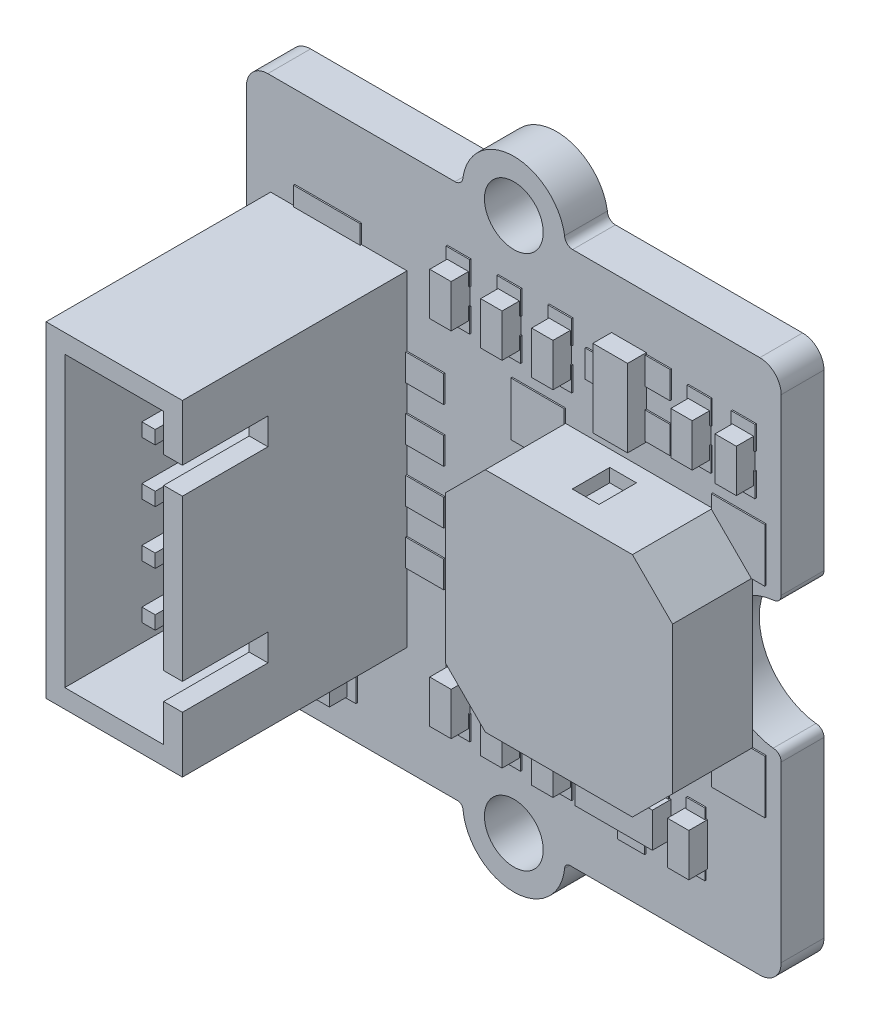
SolidWorks part; units mm, degrees
other "Buzzer_MLT8530"
other "Connecteur_Grove"
other "PCB_Seeed_107020109"
ref_plane "Plan de face" through (0, 0, 0) normal (0, 0, 1) x (1, 0, 0)
ref_plane "Plan de dessus" through (0, 0, 0) normal (0, 1, 0) x (1, 0, 0)
ref_plane "Plan de droite" through (0, 0, 0) normal (1, 0, 0) x (0, 0, -1)
sketch "Esquisse1" plane through (0, 0, 0) normal (0, 0, 1) x (1, 0, 0)
  line L0 (-9.1873, -9.9873) -> (-2.0873, -9.9873)
  line L1 (-9.1873, 10.0127) -> (-2.1873, 10.0127)
  line L2 (-9.9873, -2.6873) -> (-9.9873, -9.1873)
  line L3 (-9.9873, 2.7127) -> (-9.9873, 9.2127)
  line L4 (9.2127, -9.9873) -> (2.1127, -9.9873)
  line L5 (10.0127, 2.7127) -> (10.0127, 9.2127)
  line L6 (10.0127, -2.6873) -> (10.0127, -9.1873)
  line L7 (2.2127, 10.0127) -> (9.2127, 10.0127)
  arc A0 (-9.1873, 10.0127) -> (-9.9873, 9.2127) centre (-9.1873, 9.2127) ccw
  arc A1 (-9.9873, -9.1873) -> (-9.1873, -9.9873) centre (-9.1873, -9.1873) ccw
  arc A2 (9.2127, -9.9873) -> (10.0127, -9.1873) centre (9.2127, -9.1873) ccw
  arc A3 (9.2127, 10.0127) -> (10.0127, 9.2127) centre (9.2127, 9.2127) cw
  arc A4 (-2.0873, -9.9873) -> (-1.8873, -10.1873) centre (-2.0873, -10.1873) cw
  arc A5 (2.1127, -9.9873) -> (1.9127, -10.1873) centre (2.1127, -10.1873) ccw
  arc A6 (1.9127, -10.1873) -> (-1.8873, -10.1873) centre (0.0127, -9.9873) cw
  arc A7 (-2.1873, 10.0127) -> (-1.8873, 10.3127) centre (-2.1873, 10.3127) ccw
  arc A8 (2.2127, 10.0127) -> (1.9127, 10.3127) centre (2.2127, 10.3127) cw
  arc A9 (-1.8873, 10.3127) -> (1.9127, 10.3127) centre (0.0127, 10.0127) cw
  arc A10 (-9.9873, 2.7127) -> (-9.6873, 2.4127) centre (-9.6873, 2.7127) ccw
  arc A11 (-9.9873, -2.6873) -> (-9.6873, -2.3873) centre (-9.6873, -2.6873) cw
  arc A12 (-9.6873, -2.3873) -> (-9.6873, 2.4127) centre (-9.9873, 0.0127) ccw
  arc A13 (10.0127, -2.6873) -> (9.7127, -2.3873) centre (9.7127, -2.6873) ccw
  arc A14 (10.0127, 2.7127) -> (9.7127, 2.4127) centre (9.7127, 2.7127) cw
  arc A15 (9.7127, 2.4127) -> (9.7127, -2.3873) centre (10.0127, 0.0127) ccw
  circle A16 centre (0.0127, -9.9873) radius 1.1
  circle A17 centre (0.0127, 10.0127) radius 1.1
extrude "PCB_contour_Eagle_ep_ESTIMEE_1_6" add sketch "Esquisse1" along normal blind 1.6 separate body
sketch "Esquisse2" plane through (0, 0, 0) normal (0, 0, 1) x (1, 0, 0)
  line L1 (-9.083, -5.973) -> (-3.983, -5.973)
  line L2 (-9.083, -5.973) -> (-9.083, 6.227)
  line L3 (-9.083, 6.227) -> (-3.983, 6.227)
  line L4 (-3.983, -5.973) -> (-3.983, 6.227)
extrude "Grove_position_Eagle_H_ESTIMEE" add sketch "Esquisse2" along normal blind 8.4 from offset 1.6 separate body
sketch "Esquisse3" plane through (0, 0, 0) normal (0, 0, 1) x (1, 0, 0)
  line L1 (-8.383, -5.273) -> (-4.683, -5.273)
  line L2 (-8.383, -5.273) -> (-8.383, 5.527)
  line L3 (-8.383, 5.527) -> (-4.683, 5.527)
  line L4 (-4.683, -5.273) -> (-4.683, 5.527)
extrude "Cavite_connecteur" cut sketch "Esquisse3" against normal blind 7.3 from offset 10
sketch "Esquisse4" plane through (0, 0, 0) normal (0, 0, 1) x (1, 0, 0)
  line L1 (-4.783, -3.873) -> (-3.783, -3.873)
  line L2 (-4.783, -3.873) -> (-4.783, -2.873)
  line L3 (-4.783, -2.873) -> (-3.783, -2.873)
  line L4 (-3.783, -3.873) -> (-3.783, -2.873)
  line L6 (-4.783, 3.127) -> (-3.783, 3.127)
  line L7 (-4.783, 3.127) -> (-4.783, 4.127)
  line L8 (-4.783, 4.127) -> (-3.783, 4.127)
  line L9 (-3.783, 3.127) -> (-3.783, 4.127)
extrude "Detrompeurs_ESTIMES" cut sketch "Esquisse4" against normal blind 3.2 from offset 10
sketch "Esquisse5" plane through (0, 0, 0) normal (0, 0, 1) x (1, 0, 0)
  line L1 (-6.9, -3.123) -> (-6.4, -3.123)
  line L2 (-6.9, -3.123) -> (-6.9, -2.623)
  line L3 (-6.9, -2.623) -> (-6.4, -2.623)
  line L4 (-6.4, -3.123) -> (-6.4, -2.623)
  line L6 (-6.9, -1.123) -> (-6.4, -1.123)
  line L7 (-6.9, -1.123) -> (-6.9, -0.623)
  line L8 (-6.9, -0.623) -> (-6.4, -0.623)
  line L9 (-6.4, -1.123) -> (-6.4, -0.623)
  line L11 (-6.9, 0.877) -> (-6.4, 0.877)
  line L12 (-6.9, 0.877) -> (-6.9, 1.377)
  line L13 (-6.9, 1.377) -> (-6.4, 1.377)
  line L14 (-6.4, 0.877) -> (-6.4, 1.377)
  line L16 (-6.9, 2.877) -> (-6.4, 2.877)
  line L17 (-6.9, 2.877) -> (-6.9, 3.377)
  line L18 (-6.9, 3.377) -> (-6.4, 3.377)
  line L19 (-6.4, 2.877) -> (-6.4, 3.377)
extrude "Contacts_Grove_pas_2mm" add sketch "Esquisse5" along normal blind 5.9 from offset 2.7 separate body
sketch "Esquisse6" plane through (0, 0, 0) normal (0, 0, 1) x (1, 0, 0)
  line L0 (1.949, -4.25) -> (7.449, -4.25)
  line L1 (7.449, -4.25) -> (8.949, -2.75)
  line L2 (8.949, -2.75) -> (8.949, 2.75)
  line L3 (8.949, 2.75) -> (7.449, 4.25)
  line L4 (7.449, 4.25) -> (1.949, 4.25)
  line L5 (1.949, 4.25) -> (0.449, 2.75)
  line L6 (0.449, 2.75) -> (0.449, -2.75)
  line L7 (0.449, -2.75) -> (1.949, -4.25)
extrude "MLT8530_8_5x8_5x3" add sketch "Esquisse6" along normal blind 3 from offset 1.6 separate body
sketch "Esquisse7" plane through (0, 0, 0) normal (0, 0, 1) x (1, 0, 0)
  line L1 (4.199, 3.75) -> (5.199, 3.75)
  line L2 (4.199, 3.75) -> (4.199, 4.55)
  line L3 (4.199, 4.55) -> (5.199, 4.55)
  line L4 (5.199, 3.75) -> (5.199, 4.55)
extrude "Sortie_son_laterale_ESTIMEE" cut sketch "Esquisse7" against normal blind 1.4 from offset 3.6
sketch "Esquisse8" plane through (0, 0, 0) normal (0, 0, 1) x (1, 0, 0)
  line L1 (-0.527, 5.804) -> (0.273, 5.804)
  line L2 (-0.527, 5.804) -> (-0.527, 7.404)
  line L3 (-0.527, 7.404) -> (0.273, 7.404)
  line L4 (0.273, 5.804) -> (0.273, 7.404)
extrude "C1_position_Eagle_H_simplifiee" add sketch "Esquisse8" along normal blind 0.7 from offset 1.6 separate body
sketch "Esquisse9" plane through (0, 0, 0) normal (0, 0, 1) x (1, 0, 0)
  line L1 (-2.432, 5.804) -> (-1.632, 5.804)
  line L2 (-2.432, 5.804) -> (-2.432, 7.404)
  line L3 (-2.432, 7.404) -> (-1.632, 7.404)
  line L4 (-1.632, 5.804) -> (-1.632, 7.404)
extrude "C2_position_Eagle_H_simplifiee" add sketch "Esquisse9" along normal blind 0.7 from offset 1.6 separate body
sketch "Esquisse10" plane through (0, 0, 0) normal (0, 0, 1) x (1, 0, 0)
  line L1 (2.995, -7.254) -> (5.895, -7.254)
  line L2 (2.995, -7.254) -> (2.995, -5.954)
  line L3 (2.995, -5.954) -> (5.895, -5.954)
  line L4 (5.895, -7.254) -> (5.895, -5.954)
extrude "Q1_position_Eagle_H_simplifiee" add sketch "Esquisse10" along normal blind 0.7 from offset 1.6 separate body
sketch "Esquisse11" plane through (0, 0, 0) normal (0, 0, 1) x (1, 0, 0)
  line L1 (-0.527, -7.404) -> (0.273, -7.404)
  line L2 (-0.527, -7.404) -> (-0.527, -5.804)
  line L3 (-0.527, -5.804) -> (0.273, -5.804)
  line L4 (0.273, -7.404) -> (0.273, -5.804)
extrude "R1_position_Eagle_H_simplifiee" add sketch "Esquisse11" along normal blind 0.7 from offset 1.6 separate body
sketch "Esquisse12" plane through (0, 0, 0) normal (0, 0, 1) x (1, 0, 0)
  line L1 (3.668, 5.154) -> (4.968, 5.154)
  line L2 (3.668, 5.154) -> (3.668, 8.054)
  line L3 (3.668, 8.054) -> (4.968, 8.054)
  line L4 (4.968, 5.154) -> (4.968, 8.054)
extrude "U1_position_Eagle_H_simplifiee" add sketch "Esquisse12" along normal blind 0.7 from offset 1.6 separate body
sketch "Esquisse13" plane through (0, 0, 0) normal (0, 0, 1) x (1, 0, 0)
  line L1 (1.378, 5.804) -> (2.178, 5.804)
  line L2 (1.378, 5.804) -> (1.378, 7.404)
  line L3 (1.378, 7.404) -> (2.178, 7.404)
  line L4 (2.178, 5.804) -> (2.178, 7.404)
extrude "C3_position_Eagle_H_simplifiee" add sketch "Esquisse13" along normal blind 0.7 from offset 1.6 separate body
sketch "Esquisse14" plane through (0, 0, 0) normal (0, 0, 1) x (1, 0, 0)
  line L1 (8.236, 5.804) -> (9.036, 5.804)
  line L2 (8.236, 5.804) -> (8.236, 7.404)
  line L3 (8.236, 7.404) -> (9.036, 7.404)
  line L4 (9.036, 5.804) -> (9.036, 7.404)
extrude "C5_position_Eagle_H_simplifiee" add sketch "Esquisse14" along normal blind 0.7 from offset 1.6 separate body
sketch "Esquisse15" plane through (0, 0, 0) normal (0, 0, 1) x (1, 0, 0)
  line L1 (6.585, 5.804) -> (7.385, 5.804)
  line L2 (6.585, 5.804) -> (6.585, 7.404)
  line L3 (6.585, 7.404) -> (7.385, 7.404)
  line L4 (7.385, 5.804) -> (7.385, 7.404)
extrude "C4_position_Eagle_H_simplifiee" add sketch "Esquisse15" along normal blind 0.7 from offset 1.6 separate body
sketch "Esquisse16" plane through (0, 0, 0) normal (0, 0, 1) x (1, 0, 0)
  line L1 (-2.432, -7.404) -> (-1.632, -7.404)
  line L2 (-2.432, -7.404) -> (-2.432, -5.804)
  line L3 (-2.432, -5.804) -> (-1.632, -5.804)
  line L4 (-1.632, -7.404) -> (-1.632, -5.804)
extrude "R2_position_Eagle_H_simplifiee" add sketch "Esquisse16" along normal blind 0.7 from offset 1.6 separate body
sketch "Esquisse17" plane through (0, 0, 0) normal (0, 0, 1) x (1, 0, 0)
  line L1 (-7.785, -8.655) -> (-6.185, -8.655)
  line L2 (-7.785, -8.655) -> (-7.785, -7.855)
  line L3 (-7.785, -7.855) -> (-6.185, -7.855)
  line L4 (-6.185, -8.655) -> (-6.185, -7.855)
extrude "D1_position_Eagle_H_simplifiee" add sketch "Esquisse17" along normal blind 0.7 from offset 1.6 separate body
sketch "Esquisse18" plane through (0, 0, 0) normal (0, 0, 1) x (1, 0, 0)
  line L1 (6.458, -7.531) -> (7.258, -7.531)
  line L2 (6.458, -7.531) -> (6.458, -5.931)
  line L3 (6.458, -5.931) -> (7.258, -5.931)
  line L4 (7.258, -7.531) -> (7.258, -5.931)
extrude "D2_position_Eagle_H_simplifiee" add sketch "Esquisse18" along normal blind 0.7 from offset 1.6 separate body
sketch "Esquisse19" plane through (0, 0, 0) normal (0, 0, 1) x (1, 0, 0)
  line L1 (1.378, -7.404) -> (2.178, -7.404)
  line L2 (1.378, -7.404) -> (1.378, -5.804)
  line L3 (1.378, -5.804) -> (2.178, -5.804)
  line L4 (2.178, -7.404) -> (2.178, -5.804)
extrude "R3_position_Eagle_H_simplifiee" add sketch "Esquisse19" along normal blind 0.7 from offset 1.6 separate body
sketch "Esquisse20" plane through (0, 0, 0) normal (0, 0, 1) x (1, 0, 0)
  line L1 (-0.5715, 6.9215) -> (0.3175, 6.9215)
  line L2 (-0.5715, 6.9215) -> (-0.5715, 7.8105)
  line L3 (-0.5715, 7.8105) -> (0.3175, 7.8105)
  line L4 (0.3175, 6.9215) -> (0.3175, 7.8105)
extrude "Pad_C1_0" add sketch "Esquisse20" along normal blind 0.05 from offset 1.6 separate body
sketch "Esquisse21" plane through (0, 0, 0) normal (0, 0, 1) x (1, 0, 0)
  line L1 (-0.5715, 5.3975) -> (0.3175, 5.3975)
  line L2 (-0.5715, 5.3975) -> (-0.5715, 6.2865)
  line L3 (-0.5715, 6.2865) -> (0.3175, 6.2865)
  line L4 (0.3175, 5.3975) -> (0.3175, 6.2865)
extrude "Pad_C1_1" add sketch "Esquisse21" along normal blind 0.05 from offset 1.6 separate body
sketch "Esquisse22" plane through (0, 0, 0) normal (0, 0, 1) x (1, 0, 0)
  line L1 (-2.4765, 6.9215) -> (-1.5875, 6.9215)
  line L2 (-2.4765, 6.9215) -> (-2.4765, 7.8105)
  line L3 (-2.4765, 7.8105) -> (-1.5875, 7.8105)
  line L4 (-1.5875, 6.9215) -> (-1.5875, 7.8105)
extrude "Pad_C2_0" add sketch "Esquisse22" along normal blind 0.05 from offset 1.6 separate body
sketch "Esquisse23" plane through (0, 0, 0) normal (0, 0, 1) x (1, 0, 0)
  line L1 (-2.4765, 5.3975) -> (-1.5875, 5.3975)
  line L2 (-2.4765, 5.3975) -> (-2.4765, 6.2865)
  line L3 (-2.4765, 6.2865) -> (-1.5875, 6.2865)
  line L4 (-1.5875, 5.3975) -> (-1.5875, 6.2865)
extrude "Pad_C2_1" add sketch "Esquisse23" along normal blind 0.05 from offset 1.6 separate body
sketch "Esquisse24" plane through (0, 0, 0) normal (0, 0, 1) x (1, 0, 0)
  line L1 (-5.06, -3.373) -> (-2.56, -3.373)
  line L2 (-5.06, -3.373) -> (-5.06, -2.373)
  line L3 (-5.06, -2.373) -> (-2.56, -2.373)
  line L4 (-2.56, -3.373) -> (-2.56, -2.373)
extrude "Pad_J1_0" add sketch "Esquisse24" along normal blind 0.05 from offset 1.6 separate body
sketch "Esquisse25" plane through (0, 0, 0) normal (0, 0, 1) x (1, 0, 0)
  line L1 (-5.06, -1.373) -> (-2.56, -1.373)
  line L2 (-5.06, -1.373) -> (-5.06, -0.373)
  line L3 (-5.06, -0.373) -> (-2.56, -0.373)
  line L4 (-2.56, -1.373) -> (-2.56, -0.373)
extrude "Pad_J1_1" add sketch "Esquisse25" along normal blind 0.05 from offset 1.6 separate body
sketch "Esquisse26" plane through (0, 0, 0) normal (0, 0, 1) x (1, 0, 0)
  line L1 (-5.06, 0.627) -> (-2.56, 0.627)
  line L2 (-5.06, 0.627) -> (-5.06, 1.627)
  line L3 (-5.06, 1.627) -> (-2.56, 1.627)
  line L4 (-2.56, 0.627) -> (-2.56, 1.627)
extrude "Pad_J1_2" add sketch "Esquisse26" along normal blind 0.05 from offset 1.6 separate body
sketch "Esquisse27" plane through (0, 0, 0) normal (0, 0, 1) x (1, 0, 0)
  line L1 (-5.06, 2.627) -> (-2.56, 2.627)
  line L2 (-5.06, 2.627) -> (-5.06, 3.627)
  line L3 (-5.06, 3.627) -> (-2.56, 3.627)
  line L4 (-2.56, 2.627) -> (-2.56, 3.627)
extrude "Pad_J1_3" add sketch "Esquisse27" along normal blind 0.05 from offset 1.6 separate body
sketch "Esquisse28" plane through (0, 0, 0) normal (0, 0, 1) x (1, 0, 0)
  line L1 (-8.183, -6.673) -> (-5.683, -6.673)
  line L2 (-8.183, -6.673) -> (-8.183, -4.673)
  line L3 (-8.183, -4.673) -> (-5.683, -4.673)
  line L4 (-5.683, -6.673) -> (-5.683, -4.673)
extrude "Pad_J1_4" add sketch "Esquisse28" along normal blind 0.05 from offset 1.6 separate body
sketch "Esquisse29" plane through (0, 0, 0) normal (0, 0, 1) x (1, 0, 0)
  line L1 (-8.183, 4.927) -> (-5.683, 4.927)
  line L2 (-8.183, 4.927) -> (-8.183, 6.927)
  line L3 (-8.183, 6.927) -> (-5.683, 6.927)
  line L4 (-5.683, 4.927) -> (-5.683, 6.927)
extrude "Pad_J1_5" add sketch "Esquisse29" along normal blind 0.05 from offset 1.6 separate body
sketch "Esquisse30" plane through (0, 0, 0) normal (0, 0, 1) x (1, 0, 0)
  line L1 (3.937, -8.1915) -> (4.953, -8.1915)
  line L2 (3.937, -8.1915) -> (3.937, -7.0485)
  line L3 (3.937, -7.0485) -> (4.953, -7.0485)
  line L4 (4.953, -8.1915) -> (4.953, -7.0485)
extrude "Pad_Q1_0" add sketch "Esquisse30" along normal blind 0.05 from offset 1.6 separate body
sketch "Esquisse31" plane through (0, 0, 0) normal (0, 0, 1) x (1, 0, 0)
  line L1 (3.048, -6.1595) -> (4.064, -6.1595)
  line L2 (3.048, -6.1595) -> (3.048, -5.0165)
  line L3 (3.048, -5.0165) -> (4.064, -5.0165)
  line L4 (4.064, -6.1595) -> (4.064, -5.0165)
extrude "Pad_Q1_1" add sketch "Esquisse31" along normal blind 0.05 from offset 1.6 separate body
sketch "Esquisse32" plane through (0, 0, 0) normal (0, 0, 1) x (1, 0, 0)
  line L1 (4.826, -6.1595) -> (5.842, -6.1595)
  line L2 (4.826, -6.1595) -> (4.826, -5.0165)
  line L3 (4.826, -5.0165) -> (5.842, -5.0165)
  line L4 (5.842, -6.1595) -> (5.842, -5.0165)
extrude "Pad_Q1_2" add sketch "Esquisse32" along normal blind 0.05 from offset 1.6 separate body
sketch "Esquisse33" plane through (0, 0, 0) normal (0, 0, 1) x (1, 0, 0)
  line L1 (-0.5715, -7.8105) -> (0.3175, -7.8105)
  line L2 (-0.5715, -7.8105) -> (-0.5715, -6.9215)
  line L3 (-0.5715, -6.9215) -> (0.3175, -6.9215)
  line L4 (0.3175, -7.8105) -> (0.3175, -6.9215)
extrude "Pad_R1_0" add sketch "Esquisse33" along normal blind 0.05 from offset 1.6 separate body
sketch "Esquisse34" plane through (0, 0, 0) normal (0, 0, 1) x (1, 0, 0)
  line L1 (-0.5715, -6.2865) -> (0.3175, -6.2865)
  line L2 (-0.5715, -6.2865) -> (-0.5715, -5.3975)
  line L3 (-0.5715, -5.3975) -> (0.3175, -5.3975)
  line L4 (0.3175, -6.2865) -> (0.3175, -5.3975)
extrude "Pad_R1_1" add sketch "Esquisse34" along normal blind 0.05 from offset 1.6 separate body
sketch "Esquisse35" plane through (0, 0, 0) normal (0, 0, 1) x (1, 0, 0)
  line L1 (-0.051, -4.75) -> (1.949, -4.75)
  line L2 (-0.051, -4.75) -> (-0.051, -2.75)
  line L3 (-0.051, -2.75) -> (1.949, -2.75)
  line L4 (1.949, -4.75) -> (1.949, -2.75)
extrude "Pad_BUZ1_0" add sketch "Esquisse35" along normal blind 0.05 from offset 1.6 separate body
sketch "Esquisse36" plane through (0, 0, 0) normal (0, 0, 1) x (1, 0, 0)
  line L1 (7.449, -4.75) -> (9.449, -4.75)
  line L2 (7.449, -4.75) -> (7.449, -2.75)
  line L3 (7.449, -2.75) -> (9.449, -2.75)
  line L4 (9.449, -4.75) -> (9.449, -2.75)
extrude "Pad_BUZ1_1" add sketch "Esquisse36" along normal blind 0.05 from offset 1.6 separate body
sketch "Esquisse37" plane through (0, 0, 0) normal (0, 0, 1) x (1, 0, 0)
  line L1 (7.449, 2.75) -> (9.449, 2.75)
  line L2 (7.449, 2.75) -> (7.449, 4.75)
  line L3 (7.449, 4.75) -> (9.449, 4.75)
  line L4 (9.449, 2.75) -> (9.449, 4.75)
extrude "Pad_BUZ1_2" add sketch "Esquisse37" along normal blind 0.05 from offset 1.6 separate body
sketch "Esquisse38" plane through (0, 0, 0) normal (0, 0, 1) x (1, 0, 0)
  line L1 (-0.051, 2.75) -> (1.949, 2.75)
  line L2 (-0.051, 2.75) -> (-0.051, 4.75)
  line L3 (-0.051, 4.75) -> (1.949, 4.75)
  line L4 (1.949, 2.75) -> (1.949, 4.75)
extrude "Pad_BUZ1_3" add sketch "Esquisse38" along normal blind 0.05 from offset 1.6 separate body
sketch "Esquisse39" plane through (0, 0, 0) normal (0, 0, 1) x (1, 0, 0)
  line L1 (2.7305, 6.096) -> (3.8735, 6.096)
  line L2 (2.7305, 6.096) -> (2.7305, 7.112)
  line L3 (2.7305, 7.112) -> (3.8735, 7.112)
  line L4 (3.8735, 6.096) -> (3.8735, 7.112)
extrude "Pad_U1_0" add sketch "Esquisse39" along normal blind 0.05 from offset 1.6 separate body
sketch "Esquisse40" plane through (0, 0, 0) normal (0, 0, 1) x (1, 0, 0)
  line L1 (4.7625, 6.985) -> (5.9055, 6.985)
  line L2 (4.7625, 6.985) -> (4.7625, 8.001)
  line L3 (4.7625, 8.001) -> (5.9055, 8.001)
  line L4 (5.9055, 6.985) -> (5.9055, 8.001)
extrude "Pad_U1_1" add sketch "Esquisse40" along normal blind 0.05 from offset 1.6 separate body
sketch "Esquisse41" plane through (0, 0, 0) normal (0, 0, 1) x (1, 0, 0)
  line L1 (4.7625, 5.207) -> (5.9055, 5.207)
  line L2 (4.7625, 5.207) -> (4.7625, 6.223)
  line L3 (4.7625, 6.223) -> (5.9055, 6.223)
  line L4 (5.9055, 5.207) -> (5.9055, 6.223)
extrude "Pad_U1_2" add sketch "Esquisse41" along normal blind 0.05 from offset 1.6 separate body
sketch "Esquisse42" plane through (0, 0, 0) normal (0, 0, 1) x (1, 0, 0)
  line L1 (1.3335, 6.9215) -> (2.2225, 6.9215)
  line L2 (1.3335, 6.9215) -> (1.3335, 7.8105)
  line L3 (1.3335, 7.8105) -> (2.2225, 7.8105)
  line L4 (2.2225, 6.9215) -> (2.2225, 7.8105)
extrude "Pad_C3_0" add sketch "Esquisse42" along normal blind 0.05 from offset 1.6 separate body
sketch "Esquisse43" plane through (0, 0, 0) normal (0, 0, 1) x (1, 0, 0)
  line L1 (1.3335, 5.3975) -> (2.2225, 5.3975)
  line L2 (1.3335, 5.3975) -> (1.3335, 6.2865)
  line L3 (1.3335, 6.2865) -> (2.2225, 6.2865)
  line L4 (2.2225, 5.3975) -> (2.2225, 6.2865)
extrude "Pad_C3_1" add sketch "Esquisse43" along normal blind 0.05 from offset 1.6 separate body
sketch "Esquisse44" plane through (0, 0, 0) normal (0, 0, 1) x (1, 0, 0)
  line L1 (8.1915, 5.3975) -> (9.0805, 5.3975)
  line L2 (8.1915, 5.3975) -> (8.1915, 6.2865)
  line L3 (8.1915, 6.2865) -> (9.0805, 6.2865)
  line L4 (9.0805, 5.3975) -> (9.0805, 6.2865)
extrude "Pad_C5_0" add sketch "Esquisse44" along normal blind 0.05 from offset 1.6 separate body
sketch "Esquisse45" plane through (0, 0, 0) normal (0, 0, 1) x (1, 0, 0)
  line L1 (8.1915, 6.9215) -> (9.0805, 6.9215)
  line L2 (8.1915, 6.9215) -> (8.1915, 7.8105)
  line L3 (8.1915, 7.8105) -> (9.0805, 7.8105)
  line L4 (9.0805, 6.9215) -> (9.0805, 7.8105)
extrude "Pad_C5_1" add sketch "Esquisse45" along normal blind 0.05 from offset 1.6 separate body
sketch "Esquisse46" plane through (0, 0, 0) normal (0, 0, 1) x (1, 0, 0)
  line L1 (6.5405, 5.3975) -> (7.4295, 5.3975)
  line L2 (6.5405, 5.3975) -> (6.5405, 6.2865)
  line L3 (6.5405, 6.2865) -> (7.4295, 6.2865)
  line L4 (7.4295, 5.3975) -> (7.4295, 6.2865)
extrude "Pad_C4_0" add sketch "Esquisse46" along normal blind 0.05 from offset 1.6 separate body
sketch "Esquisse47" plane through (0, 0, 0) normal (0, 0, 1) x (1, 0, 0)
  line L1 (6.5405, 6.9215) -> (7.4295, 6.9215)
  line L2 (6.5405, 6.9215) -> (6.5405, 7.8105)
  line L3 (6.5405, 7.8105) -> (7.4295, 7.8105)
  line L4 (7.4295, 6.9215) -> (7.4295, 7.8105)
extrude "Pad_C4_1" add sketch "Esquisse47" along normal blind 0.05 from offset 1.6 separate body
sketch "Esquisse48" plane through (0, 0, 0) normal (0, 0, 1) x (1, 0, 0)
  line L1 (-2.4765, -7.8105) -> (-1.5875, -7.8105)
  line L2 (-2.4765, -7.8105) -> (-2.4765, -6.9215)
  line L3 (-2.4765, -6.9215) -> (-1.5875, -6.9215)
  line L4 (-1.5875, -7.8105) -> (-1.5875, -6.9215)
extrude "Pad_R2_0" add sketch "Esquisse48" along normal blind 0.05 from offset 1.6 separate body
sketch "Esquisse49" plane through (0, 0, 0) normal (0, 0, 1) x (1, 0, 0)
  line L1 (-2.4765, -6.2865) -> (-1.5875, -6.2865)
  line L2 (-2.4765, -6.2865) -> (-2.4765, -5.3975)
  line L3 (-2.4765, -5.3975) -> (-1.5875, -5.3975)
  line L4 (-1.5875, -6.2865) -> (-1.5875, -5.3975)
extrude "Pad_R2_1" add sketch "Esquisse49" along normal blind 0.05 from offset 1.6 separate body
sketch "Esquisse50" plane through (0, 0, 0) normal (0, 0, 1) x (1, 0, 0)
  line L1 (-6.604, -8.6995) -> (-5.842, -8.6995)
  line L2 (-6.604, -8.6995) -> (-6.604, -7.8105)
  line L3 (-6.604, -7.8105) -> (-5.842, -7.8105)
  line L4 (-5.842, -8.6995) -> (-5.842, -7.8105)
extrude "Pad_D1_0" add sketch "Esquisse50" along normal blind 0.05 from offset 1.6 separate body
sketch "Esquisse51" plane through (0, 0, 0) normal (0, 0, 1) x (1, 0, 0)
  line L1 (-8.128, -8.6995) -> (-7.366, -8.6995)
  line L2 (-8.128, -8.6995) -> (-8.128, -7.8105)
  line L3 (-8.128, -7.8105) -> (-7.366, -7.8105)
  line L4 (-7.366, -8.6995) -> (-7.366, -7.8105)
extrude "Pad_D1_1" add sketch "Esquisse51" along normal blind 0.05 from offset 1.6 separate body
sketch "Esquisse52" plane through (0, 0, 0) normal (0, 0, 1) x (1, 0, 0)
  line L1 (6.508, -7.912) -> (7.208, -7.912)
  line L2 (6.508, -7.912) -> (6.508, -7.15)
  line L3 (6.508, -7.15) -> (7.208, -7.15)
  line L4 (7.208, -7.912) -> (7.208, -7.15)
extrude "Pad_D2_0" add sketch "Esquisse52" along normal blind 0.05 from offset 1.6 separate body
sketch "Esquisse53" plane through (0, 0, 0) normal (0, 0, 1) x (1, 0, 0)
  line L1 (6.508, -6.312) -> (7.208, -6.312)
  line L2 (6.508, -6.312) -> (6.508, -5.55)
  line L3 (6.508, -5.55) -> (7.208, -5.55)
  line L4 (7.208, -6.312) -> (7.208, -5.55)
extrude "Pad_D2_1" add sketch "Esquisse53" along normal blind 0.05 from offset 1.6 separate body
sketch "Esquisse54" plane through (0, 0, 0) normal (0, 0, 1) x (1, 0, 0)
  line L1 (1.3335, -7.8105) -> (2.2225, -7.8105)
  line L2 (1.3335, -7.8105) -> (1.3335, -6.9215)
  line L3 (1.3335, -6.9215) -> (2.2225, -6.9215)
  line L4 (2.2225, -7.8105) -> (2.2225, -6.9215)
extrude "Pad_R3_0" add sketch "Esquisse54" along normal blind 0.05 from offset 1.6 separate body
sketch "Esquisse55" plane through (0, 0, 0) normal (0, 0, 1) x (1, 0, 0)
  line L1 (1.3335, -6.2865) -> (2.2225, -6.2865)
  line L2 (1.3335, -6.2865) -> (1.3335, -5.3975)
  line L3 (1.3335, -5.3975) -> (2.2225, -5.3975)
  line L4 (2.2225, -6.2865) -> (2.2225, -5.3975)
extrude "Pad_R3_1" add sketch "Esquisse55" along normal blind 0.05 from offset 1.6 separate body
